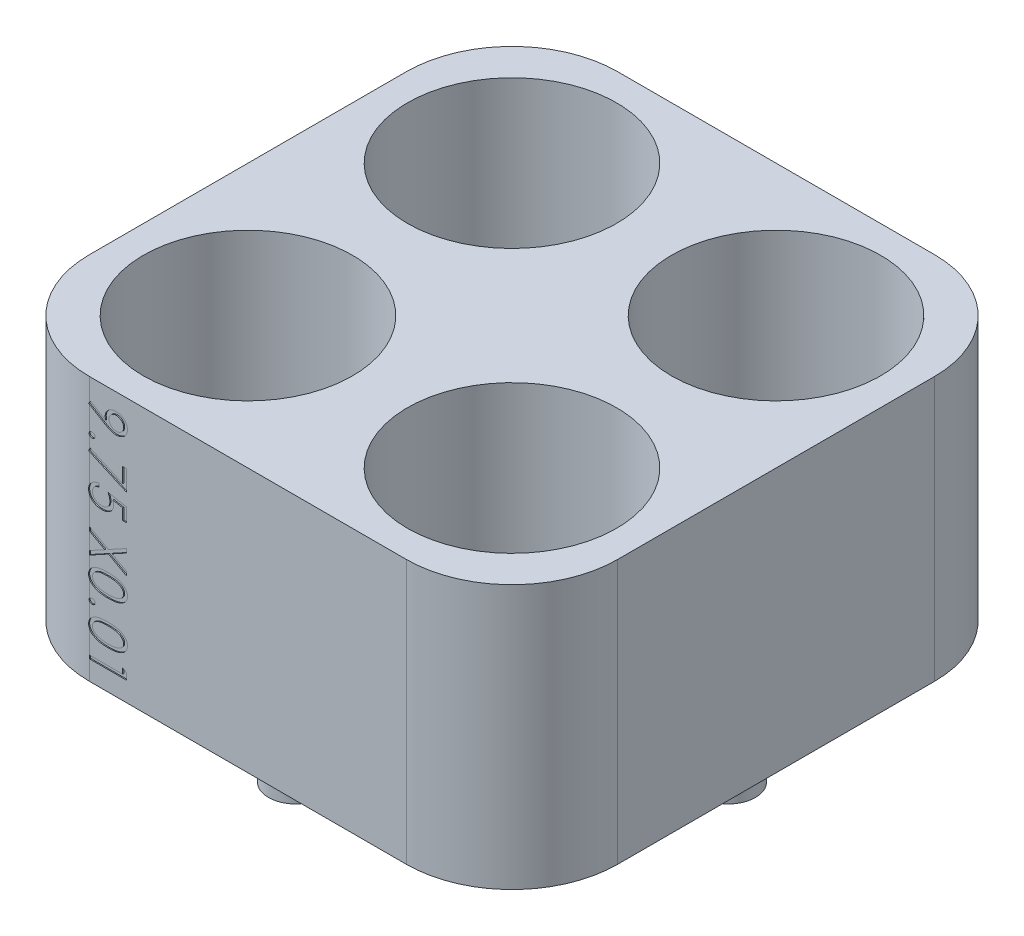
SolidWorks part; units mm, degrees
ref_plane "Alzado" through (0, 0, 0) normal (0, 0, 1) x (1, 0, 0)
ref_plane "Planta" through (0, 0, 0) normal (0, 1, 0) x (1, 0, 0)
ref_plane "Vista lateral" through (0, 0, 0) normal (1, 0, 0) x (0, 0, -1)
sketch "Croquis1" plane through (0, 0, 0) normal (0, 1, 0) x (1, 0, 0)
  line L1 (-25, 25) -> (25, 25)
  line L2 (-25, 25) -> (-25, -25)
  line L3 (-25, -25) -> (25, -25)
  line L4 (25, 25) -> (25, -25)
  line L5 (-25, 25) -> (25, -25) construction
  line L6 (-25, -25) -> (25, 25) construction
  point P0 (0, 0)
  dimension "D1" = 50
  dimension "D2" = 50
extrude "Saliente-Extruir1" add sketch "Croquis1" along normal blind 25
sketch "Croquis2" plane through (0, 25, 0) normal (0, 1, 0) x (1, 0, 0)
  line L1 (-25, 25) -> (-25, -25) construction
  line L2 (25, 25) -> (-25, 25) construction
  circle A0 centre (-12.5, 12.5) radius 9.9
  dimension "D1" = 19.8
  dimension "D2" = 12.5
  dimension "D3" = 12.5
extrude "Cortar-Extruir1" cut sketch "Croquis2" against normal blind 34
pattern_linear "MatrizL1" count 2 spacing 25 along (1, 0, 0) count 2 spacing 25 along (0, 0, 1) of "Cortar-Extruir1"
sketch "Croquis3" plane through (0, 0, 0) normal (0, -1, 0) x (1, 0, 0)
  line L0 (0, 7.2028) -> (0, 11.424) construction
  line L1 (-2.55, 0) -> (-5.3602, 0) construction
  circle A0 centre (0, 0) radius 2.55
  circle A1 centre (20.5, 0) radius 2.55
  circle A2 centre (-20.5, 0) radius 2.55
  circle A3 centre (0, 20.5) radius 2.55
  circle A4 centre (0, -20.5) radius 2.55
  dimension "D1" = 5.1
  dimension "D2" = 5.1
  dimension "D5" = 5.1
  dimension "D3" = 20.5
  dimension "D4" = 20.5
extrude "Saliente-Extruir2" add sketch "Croquis3" along normal blind 3
fillet "Redondeo3" radius 10 4 edges at (-25, 12.5, -25) (25, 12.5, -25) (25, 12.5, 25) (-25, 12.5, 25)
sketch "Croquis6" plane through (25, 0, 0) normal (1, 0, 0) x (0, 0, -1)
  line L5 (-15, 25) -> (15, 25) construction
  line L6 (-1.0144, 25) -> (5.0005, 25)
  line L7 (-1.0144, 25) -> (-1.0144, 23.8299)
  line L8 (-1.0144, 23.8299) -> (5.0005, 23.8299)
  line L9 (5.0005, 25) -> (5.0005, 23.8299)
sketch "Croquis7" plane through (0, 0, -25) normal (0, 0, -1) x (-1, 0, 0)
  line L0 (7.8632, 14.1683) -> (8.4844, 13.6947)
  line L1 (8.4844, 13.6947) -> (9.1494, 13.7051)
  line L2 (10.3053, 7.9462) -> (10.3053, 7.1749)
  line L3 (10.3053, 7.1749) -> (10.031, 7.1749)
  line L4 (10.031, 7.1749) -> (9.7567, 7.1749)
  line L5 (9.7567, 7.1749) -> (9.7567, 7.9064)
  line L6 (8.8152, 8.9851) -> (8.2479, 8.958)
  line L7 (8.2479, 8.958) -> (8.2217, 8.0664)
  line L8 (8.2217, 8.0664) -> (8.1956, 7.1749)
  line L9 (8.1956, 7.1749) -> (7.9246, 7.1749)
  line L10 (7.9246, 7.1749) -> (7.6536, 7.1749)
  line L11 (7.6536, 7.1749) -> (7.6536, 8.2734)
  line L12 (7.6536, 8.2734) -> (7.6536, 9.372)
  line L13 (7.6536, 9.372) -> (7.3564, 9.6424)
  line L14 (-2.7058, 14.0872) -> (-2.3467, 13.6793)
  line L15 (-2.3467, 13.6793) -> (-1.6645, 14.3361)
  line L16 (-1.6495, 11.3447) -> (-2.312, 11.9941)
  line L17 (-2.312, 11.9941) -> (-2.981, 11.3447)
  line L18 (-9.4499, 8.7294) -> (-8.8056, 8.7294)
  line L19 (-8.8056, 8.7294) -> (-8.8056, 8.455)
  line L20 (-8.8056, 8.455) -> (-8.8056, 8.1807)
  line L21 (-8.8056, 8.1807) -> (-9.4064, 8.1807)
  line L22 (-9.2629, 7.7692) -> (-8.577, 7.7692)
  line L23 (-8.577, 7.7692) -> (-8.577, 8.3636)
  line L24 (-8.577, 8.3636) -> (-8.577, 8.958)
  line L25 (-8.577, 8.958) -> (-9.2857, 8.9847)
  line L26 (-9.2857, 8.9847) -> (-9.9944, 9.0114)
  line L27 (-9.9944, 9.0114) -> (-9.9944, 9.2818)
  line L28 (-9.9944, 9.2818) -> (-9.9944, 9.5523)
  line L29 (-9.9944, 9.5523) -> (-9.304, 9.5523)
  line L30 (-5.4224, 9.2818) -> (-5.4224, 9.0114)
  line L31 (-5.4224, 9.0114) -> (-6.131, 8.9847)
  line L32 (-6.131, 8.9847) -> (-6.8397, 8.958)
  line L33 (-6.8397, 8.958) -> (-6.8659, 8.0664)
  line L34 (-6.8659, 8.0664) -> (-6.892, 7.1749)
  line L35 (-6.892, 7.1749) -> (-7.163, 7.1749)
  line L36 (-7.163, 7.1749) -> (-7.434, 7.1749)
  line L37 (-7.434, 7.1749) -> (-7.434, 8.1741)
  line L38 (-6.1873, 9.5523) -> (-5.4224, 9.5523)
  line L39 (-5.4224, 9.5523) -> (-5.4224, 9.2818)
  line L40 (-2.9535, 9.278) -> (-2.9535, 9.0037)
  line L41 (-2.9535, 9.0037) -> (-3.621, 9.0037)
  line L42 (-4.508, 7.9796) -> (-4.508, 7.1749)
  line L43 (-4.508, 7.1749) -> (-4.7906, 7.1749)
  line L44 (-4.7906, 7.1749) -> (-5.0732, 7.1749)
  line L45 (-5.0732, 7.1749) -> (-5.0421, 8.1431)
  line L46 (-3.7256, 9.5523) -> (-2.9535, 9.5523)
  line L47 (-2.9535, 9.5523) -> (-2.9535, 9.278)
  line L48 (-1.1662, 7.9978) -> (-1.8562, 7.9978)
  line L49 (-1.8562, 7.9978) -> (-1.8562, 8.2722)
  line L50 (-1.8562, 8.2722) -> (-1.8562, 8.5465)
  line L51 (-1.8562, 8.5465) -> (-1.2098, 8.5465)
  line L52 (-1.3075, 8.958) -> (-1.9934, 8.958)
  line L53 (-1.9934, 8.958) -> (-1.9934, 8.3636)
  line L54 (-1.9934, 8.3636) -> (-1.9934, 7.7692)
  line L55 (-1.9934, 7.7692) -> (-1.3761, 7.7422)
  line L56 (-1.3761, 7.7422) -> (-0.7589, 7.7152)
  line L57 (-0.7589, 7.7152) -> (-0.7589, 7.4353)
  line L58 (-0.7589, 7.4353) -> (-0.7589, 7.1555)
  line L59 (-0.7589, 7.1555) -> (-1.4994, 7.1891)
  line L60 (2.4415, 9.2818) -> (2.4415, 9.0114)
  line L61 (2.4415, 9.0114) -> (1.7328, 8.9847)
  line L62 (1.7328, 8.9847) -> (1.0242, 8.958)
  line L63 (1.0242, 8.958) -> (0.998, 8.0664)
  line L64 (0.998, 8.0664) -> (0.9718, 7.1749)
  line L65 (0.9718, 7.1749) -> (0.7008, 7.1749)
  line L66 (0.7008, 7.1749) -> (0.4298, 7.1749)
  line L67 (0.4298, 7.1749) -> (0.4298, 8.1741)
  line L68 (1.6766, 9.5523) -> (2.4415, 9.5523)
  line L69 (2.4415, 9.5523) -> (2.4415, 9.2818)
  line L70 (3.6718, 8.7294) -> (4.3617, 8.7294)
  line L71 (4.3617, 8.7294) -> (4.3617, 8.455)
  line L72 (4.3617, 8.455) -> (4.3617, 8.1807)
  line L73 (4.3617, 8.1807) -> (3.7153, 8.1807)
  line L74 (3.7641, 9.0037) -> (3.0816, 9.0037)
  line L75 (3.0816, 9.0037) -> (3.0816, 9.278)
  line L76 (3.0816, 9.278) -> (3.0816, 9.5523)
  line L77 (3.0816, 9.5523) -> (3.863, 9.5523)
  line L78 (7.1049, 8.3636) -> (7.1049, 7.1749)
  line L79 (7.1049, 7.1749) -> (6.8306, 7.1749)
  line L80 (6.8306, 7.1749) -> (6.5563, 7.1749)
  line L81 (6.5563, 7.1749) -> (6.5563, 8.3636)
  line L82 (6.5563, 8.3636) -> (6.5563, 9.5523)
  line L83 (6.5563, 9.5523) -> (6.8306, 9.5523)
  line L84 (6.8306, 9.5523) -> (7.1049, 9.5523)
  line L85 (7.1049, 9.5523) -> (7.1049, 8.3636)
  line L86 (0.8827, 14.6336) -> (0.7629, 14.6662)
  line L87 (-13.4691, 8.7327) -> (-13.4691, 7.7235)
  line L88 (-13.4691, 7.7235) -> (-12.4632, 7.7235)
  line L89 (-12.4632, 7.7235) -> (-11.4574, 7.7235)
  line L90 (-11.4574, 7.7235) -> (-11.4574, 7.9795)
  line L91 (-12.4358, 8.455) -> (-13.1948, 8.455)
  line L92 (-13.1948, 8.455) -> (-13.1948, 8.719)
  line L93 (-12.5776, 9.7156) -> (-13.4691, 9.7418)
  line L94 (-13.4691, 9.7418) -> (-13.4691, 8.7327)
  arc A0 (7.8207, 15.7172) -> (7.8364, 15.7705) centre (7.7385, 15.7705) ccw
  arc A1 (7.7403, 15.5996) -> (7.8207, 15.7172) centre (5.4553, 17.249) ccw
  arc A2 (7.6344, 15.4624) -> (7.7403, 15.5996) centre (5.511, 17.2088) ccw
  arc A3 (7.509, 15.3169) -> (7.6344, 15.4624) centre (4.4381, 18.0912) ccw
  arc A4 (7.509, 15.3169) -> (7.3859, 15.1667) centre (9.0083, 13.9623) ccw
  arc A5 (7.3859, 15.1667) -> (7.2866, 15.015) centre (8.617, 14.2528) ccw
  arc A6 (7.2866, 15.015) -> (7.2205, 14.8813) centre (8.3511, 14.4051) ccw
  arc A7 (7.2205, 14.8813) -> (7.2118, 14.7982) centre (7.3529, 14.8255) ccw
  arc A8 (7.2118, 14.7982) -> (7.2549, 14.7131) centre (7.3828, 14.8313) ccw
  arc A9 (7.2549, 14.7131) -> (7.4157, 14.5487) centre (10.2671, 17.4976) ccw
  arc A10 (7.4157, 14.5487) -> (7.6231, 14.3611) centre (10.3207, 17.5531) ccw
  arc A11 (7.6231, 14.3611) -> (7.8632, 14.1683) centre (11.5806, 19.0439) ccw
  arc A12 (9.1494, 13.7051) -> (9.6224, 13.7371) centre (9.0782, 18.267) ccw
  arc A13 (9.6224, 13.7371) -> (9.942, 13.8238) centre (9.4861, 14.8713) ccw
  arc A14 (9.942, 13.8238) -> (10.2456, 14.0053) centre (9.39, 15.0921) ccw
  arc A15 (10.2456, 14.0053) -> (10.6786, 14.3706) centre (5.0774, 20.5705) ccw
  arc A16 (10.6786, 14.3706) -> (10.8157, 14.5072) centre (9.344, 15.8478) ccw
  arc A17 (10.8157, 14.5072) -> (10.9316, 14.6498) centre (9.6175, 15.5987) ccw
  arc A18 (10.9316, 14.6498) -> (11.0142, 14.7795) centre (9.864, 15.4207) ccw
  arc A19 (11.0142, 14.7795) -> (11.0368, 14.8667) centre (10.8577, 14.8667) ccw
  arc A20 (11.0368, 14.8667) -> (11.0138, 14.9543) centre (10.8588, 14.8667) ccw
  arc A21 (11.0138, 14.9543) -> (10.9294, 15.0856) centre (9.8293, 14.2855) ccw
  arc A22 (10.9294, 15.0856) -> (10.8111, 15.2305) centre (9.5779, 14.1027) ccw
  arc A23 (10.8111, 15.2305) -> (10.6711, 15.3696) centre (9.282, 13.8321) ccw
  arc A24 (10.531, 15.5023) -> (10.6711, 15.3696) centre (13.4494, 18.4448) ccw
  arc A25 (10.4128, 15.6274) -> (10.531, 15.5023) centre (12.3843, 17.371) ccw
  arc A26 (10.3221, 15.7353) -> (10.4128, 15.6274) centre (12.5085, 17.4808) ccw
  arc A27 (10.3053, 15.7832) -> (10.3221, 15.7353) centre (10.3821, 15.7832) ccw
  arc A28 (10.3608, 15.8219) -> (10.3053, 15.7832) centre (10.3466, 15.7832) ccw
  arc A29 (10.5656, 15.7289) -> (10.3608, 15.8219) centre (9.8279, 14.3762) ccw
  arc A30 (10.8002, 15.5792) -> (10.5656, 15.7289) centre (9.599, 13.9564) ccw
  arc A31 (10.9826, 15.4138) -> (10.8002, 15.5792) centre (10.0591, 14.578) ccw
  arc A32 (10.9826, 15.4138) -> (11.0637, 15.3403) centre (11.3967, 15.7885) ccw
  arc A33 (11.0637, 15.3403) -> (11.1631, 15.2781) centre (11.5017, 15.9299) ccw
  arc A34 (11.1631, 15.2781) -> (11.265, 15.2354) centre (11.4705, 15.8698) ccw
  arc A35 (11.265, 15.2354) -> (11.3528, 15.2216) centre (11.3528, 15.5063) ccw
  arc A36 (11.5105, 15.1947) -> (11.3528, 15.2216) centre (11.3528, 14.7446) ccw
  arc A37 (11.6455, 15.1174) -> (11.5105, 15.1947) centre (11.3692, 14.7916) ccw
  arc A38 (11.7362, 15.0028) -> (11.6455, 15.1174) centre (11.405, 14.8338) ccw
  arc A39 (11.7684, 14.8692) -> (11.7362, 15.0028) centre (11.4744, 14.8692) ccw
  arc A40 (11.7684, 14.8692) -> (11.79, 14.7971) centre (11.8993, 14.8692) ccw
  arc A41 (11.79, 14.7971) -> (11.8825, 14.6685) centre (13.4278, 15.8772) ccw
  arc A42 (11.8825, 14.6685) -> (12.0082, 14.5215) centre (13.633, 16.0377) ccw
  arc A43 (12.0082, 14.5215) -> (12.157, 14.3724) centre (14.2933, 16.654) ccw
  arc A44 (12.438, 14.0823) -> (12.157, 14.3724) centre (9.3325, 11.356) ccw
  arc A45 (12.4278, 13.9645) -> (12.438, 14.0823) centre (12.3765, 14.0283) ccw
  arc A46 (12.2881, 13.9582) -> (12.4278, 13.9645) centre (12.3537, 14.0566) ccw
  arc A47 (11.9498, 14.2059) -> (12.2881, 13.9582) centre (14.8744, 17.8451) ccw
  arc A48 (11.9498, 14.2059) -> (11.8015, 14.3147) centre (10.6506, 12.5892) ccw
  arc A49 (11.8015, 14.3147) -> (11.6481, 14.4066) centre (10.7739, 12.7741) ccw
  arc A50 (11.6481, 14.4066) -> (11.5101, 14.4719) centre (10.9149, 13.0372) ccw
  arc A51 (11.5101, 14.4719) -> (11.4191, 14.4901) centre (11.4191, 14.2524) ccw
  arc A52 (11.4191, 14.4901) -> (11.2737, 14.4365) centre (11.4191, 14.2662) ccw
  arc A53 (11.2737, 14.4365) -> (11.0199, 14.2002) centre (13.8839, 11.378) ccw
  arc A54 (11.0199, 14.2002) -> (10.703, 13.8512) centre (15.1341, 10.1459) ccw
  arc A55 (10.703, 13.8512) -> (10.3171, 13.3718) centre (23.3414, 3.2831) ccw
  arc A56 (10.3171, 13.3718) -> (10.2657, 13.2677) centre (10.5478, 13.1931) ccw
  arc A57 (10.2657, 13.2677) -> (10.2276, 13.0849) centre (11.9738, 12.816) ccw
  arc A58 (10.2276, 13.0849) -> (10.2027, 12.8512) centre (12.7023, 12.7038) ccw
  arc A59 (10.2027, 12.8512) -> (10.1946, 12.5765) centre (14.86, 12.5765) ccw
  arc A60 (10.1946, 12.5765) -> (10.204, 12.2376) centre (16.3162, 12.5765) ccw
  arc A61 (10.204, 12.2376) -> (10.2357, 12.0059) centre (11.6523, 12.3179) ccw
  arc A62 (10.2357, 12.0059) -> (10.2978, 11.8205) centre (11.1359, 12.2042) ccw
  arc A63 (10.2978, 11.8205) -> (10.4015, 11.6373) centre (11.4166, 12.3327) ccw
  arc A64 (10.4015, 11.6373) -> (10.6632, 11.2924) centre (14.0932, 14.1663) ccw
  arc A65 (10.6632, 11.2924) -> (10.9626, 10.9662) centre (14.4096, 14.4314) ccw
  arc A66 (10.9626, 10.9662) -> (11.2451, 10.7049) centre (14.694, 14.7173) ccw
  arc A67 (11.2451, 10.7049) -> (11.3944, 10.6496) centre (11.3944, 10.8787) ccw
  arc A68 (11.3944, 10.6496) -> (11.4678, 10.669) centre (11.3944, 10.7979) ccw
  arc A69 (11.4678, 10.669) -> (11.591, 10.7467) centre (10.6583, 12.0903) ccw
  arc A70 (11.591, 10.7467) -> (11.7308, 10.8535) centre (10.4984, 12.3206) ccw
  arc A71 (11.7308, 10.8535) -> (11.8705, 10.98) centre (10.1105, 12.7824) ccw
  arc A72 (12.1865, 11.2633) -> (11.8705, 10.98) centre (15.333, 7.434) ccw
  arc A73 (12.3254, 11.2717) -> (12.1865, 11.2633) centre (12.2618, 11.1718) ccw
  arc A74 (12.3462, 11.1583) -> (12.3254, 11.2717) centre (12.2831, 11.2053) ccw
  arc A75 (12.0866, 10.8425) -> (12.3462, 11.1583) centre (8.8334, 13.7815) ccw
  arc A76 (12.0866, 10.8425) -> (11.9503, 10.6793) centre (14.1042, 9.0197) ccw
  arc A77 (11.9503, 10.6793) -> (11.8331, 10.5124) centre (13.7779, 9.2711) ccw
  arc A78 (11.8331, 10.5124) -> (11.7469, 10.3632) centre (13.4831, 9.4593) ccw
  arc A79 (11.7469, 10.3632) -> (11.7198, 10.2678) centre (11.9646, 10.2498) ccw
  arc A80 (11.6821, 10.1339) -> (11.7198, 10.2678) centre (11.3722, 10.2934) ccw
  arc A81 (11.5944, 10.0217) -> (11.6821, 10.1339) centre (11.3432, 10.3083) ccw
  arc A82 (11.4687, 9.9467) -> (11.5944, 10.0217) centre (11.3273, 10.3265) ccw
  arc A83 (11.3222, 9.9195) -> (11.4687, 9.9467) centre (11.3174, 10.353) ccw
  arc A84 (11.3222, 9.9195) -> (11.2525, 9.9004) centre (11.3238, 9.7769) ccw
  arc A85 (11.2525, 9.9004) -> (11.124, 9.8199) centre (12.3164, 8.0596) ccw
  arc A86 (11.124, 9.8199) -> (10.9761, 9.711) centre (12.4479, 7.8656) ccw
  arc A87 (10.9761, 9.711) -> (10.8246, 9.5823) centre (12.9922, 7.183) ccw
  arc A88 (10.5215, 9.3355) -> (10.8246, 9.5823) centre (8.2644, 12.4162) ccw
  arc A89 (10.4143, 9.3612) -> (10.5215, 9.3355) centre (10.4788, 9.3938) ccw
  arc A90 (10.43, 9.5064) -> (10.4143, 9.3612) centre (10.534, 9.4217) ccw
  arc A91 (10.7064, 9.816) -> (10.43, 9.5064) centre (14.0228, 6.5776) ccw
  arc A92 (10.7064, 9.816) -> (10.8329, 9.9529) centre (8.2825, 12.1828) ccw
  arc A93 (10.8329, 9.9529) -> (10.9398, 10.0845) centre (9.0895, 11.4772) ccw
  arc A94 (10.9398, 10.0845) -> (11.0198, 10.1981) centre (9.1777, 11.4109) ccw
  arc A95 (11.0198, 10.1981) -> (11.0368, 10.255) centre (10.9335, 10.255) ccw
  arc A96 (11.0368, 10.255) -> (10.9841, 10.3809) centre (10.86, 10.255) ccw
  arc A97 (10.9841, 10.3809) -> (10.491, 10.8589) centre (-17.2866, -18.295) ccw
  arc A98 (10.491, 10.8589) -> (9.9956, 11.3213) centre (-12.443, -13.2114) ccw
  arc A99 (9.9956, 11.3213) -> (9.8429, 11.3925) centre (9.806, 11.1141) ccw
  arc A100 (9.8429, 11.3925) -> (9.4672, 11.4208) centre (9.4061, 8.0975) ccw
  arc A101 (9.4672, 11.4208) -> (8.9452, 11.4189) centre (9.2489, -0.4536) ccw
  arc A102 (8.9452, 11.4189) -> (8.4316, 11.3984) centre (9.4014, -6.4151) ccw
  arc A103 (8.4316, 11.3984) -> (8.2536, 11.3519) centre (8.4566, 10.9386) ccw
  arc A104 (8.2536, 11.3519) -> (7.9869, 11.175) centre (8.8016, 10.2362) ccw
  arc A105 (7.9869, 11.175) -> (7.6125, 10.8268) centre (12.8611, 5.5589) ccw
  arc A106 (7.6125, 10.8268) -> (7.2577, 10.4565) centre (15.4297, 2.9809) ccw
  arc A107 (7.2577, 10.4565) -> (7.1964, 10.2985) centre (7.4305, 10.2985) ccw
  arc A108 (7.1964, 10.2985) -> (7.2145, 10.2244) centre (7.3572, 10.2985) ccw
  arc A109 (7.2145, 10.2244) -> (7.2822, 10.1089) centre (8.3772, 10.8285) ccw
  arc A110 (7.2822, 10.1089) -> (7.3767, 9.9798) centre (8.6008, 10.9755) ccw
  arc A111 (7.3767, 9.9798) -> (7.4886, 9.8538) centre (8.8808, 11.2032) ccw
  arc A112 (7.4886, 9.8538) -> (7.6904, 9.6721) centre (8.9275, 11.2485) ccw
  arc A113 (7.6904, 9.6721) -> (7.8549, 9.5907) centre (7.9674, 10.025) ccw
  arc A114 (7.8549, 9.5907) -> (8.0864, 9.5585) centre (8.1095, 10.5738) ccw
  arc A115 (8.0864, 9.5585) -> (8.6545, 9.552) centre (8.6644, 35.0044) ccw
  arc A116 (9.1215, 9.544) -> (8.6545, 9.552) centre (8.649, -4.5201) ccw
  arc A117 (9.4164, 9.5162) -> (9.1215, 9.544) centre (9.0393, 7.0978) ccw
  arc A118 (9.6332, 9.4615) -> (9.4164, 9.5162) centre (9.2303, 8.3229) ccw
  arc A119 (9.8275, 9.3691) -> (9.6332, 9.4615) centre (9.2866, 8.4818) ccw
  arc A120 (10.07, 9.1656) -> (9.8275, 9.3691) centre (9.2785, 8.4685) ccw
  arc A121 (10.2136, 8.9165) -> (10.07, 9.1656) centre (9.5244, 8.685) ccw
  arc A122 (10.2855, 8.5518) -> (10.2136, 8.9165) centre (8.8473, 8.4577) ccw
  arc A123 (10.3053, 7.9462) -> (10.2855, 8.5518) centre (1.0313, 7.9462) ccw
  arc A124 (9.7567, 7.9064) -> (9.7228, 8.5244) centre (4.1088, 7.9064) ccw
  arc A125 (9.7228, 8.5244) -> (9.5911, 8.8245) centre (9.1787, 8.4645) ccw
  arc A126 (9.5911, 8.8245) -> (9.3262, 8.9654) centre (9.2738, 8.5476) ccw
  arc A127 (9.3262, 8.9654) -> (8.8152, 8.9851) centre (8.9569, 6.0198) ccw
  arc A128 (7.3564, 9.6424) -> (7.2288, 9.746) centre (6.3626, 8.55) ccw
  arc A129 (7.2288, 9.746) -> (7.0914, 9.8341) centre (6.3868, 8.5834) ccw
  arc A130 (7.0914, 9.8341) -> (6.9639, 9.8963) centre (6.5037, 8.7908) ccw
  arc A131 (6.9639, 9.8963) -> (6.8717, 9.9154) centre (6.8682, 9.6665) ccw
  arc A132 (6.7131, 9.9457) -> (6.8717, 9.9154) centre (6.8784, 10.381) ccw
  arc A133 (6.5817, 10.028) -> (6.7131, 9.9457) centre (6.8541, 10.3171) ccw
  arc A134 (6.4953, 10.1513) -> (6.5817, 10.028) centre (6.8364, 10.2983) ccw
  arc A135 (6.4648, 10.2988) -> (6.4953, 10.1513) centre (6.8376, 10.2988) ccw
  arc A136 (6.4648, 10.2988) -> (6.4415, 10.3832) centre (6.3005, 10.2988) ccw
  arc A137 (6.4415, 10.3832) -> (6.3508, 10.5191) centre (5.0271, 9.5374) ccw
  arc A138 (6.3508, 10.5191) -> (6.2253, 10.6717) centre (4.7662, 9.3438) ccw
  arc A139 (6.2253, 10.6717) -> (6.0768, 10.8221) centre (4.3143, 8.9327) ccw
  arc A140 (5.9325, 10.9654) -> (6.0768, 10.8221) centre (8.2667, 13.1698) ccw
  arc A141 (5.8213, 11.0963) -> (5.9325, 10.9654) centre (7.1292, 12.0955) ccw
  arc A142 (5.7469, 11.2041) -> (5.8213, 11.0963) centre (6.8945, 11.9163) ccw
  arc A143 (5.7519, 11.2473) -> (5.7469, 11.2041) centre (5.7767, 11.2225) ccw
  arc A144 (5.8578, 11.2647) -> (5.7519, 11.2473) centre (5.8169, 11.1823) ccw
  arc A145 (6.131, 11.1127) -> (5.8578, 11.2647) centre (4.3782, 8.2823) ccw
  arc A146 (6.3917, 10.9301) -> (6.131, 11.1127) centre (4.6509, 8.7227) ccw
  arc A147 (6.4986, 10.7849) -> (6.3917, 10.9301) centre (6.1812, 10.6631) ccw
  arc A148 (6.4986, 10.7849) -> (6.6024, 10.6772) centre (6.6776, 10.8536) ccw
  arc A149 (6.6024, 10.6772) -> (6.7608, 10.6678) centre (6.6948, 10.8938) ccw
  arc A150 (6.7608, 10.6678) -> (6.9698, 10.7749) centre (6.5856, 11.2676) ccw
  arc A151 (6.9698, 10.7749) -> (7.2092, 10.9925) centre (5.6507, 12.4663) ccw
  arc A152 (7.2092, 10.9925) -> (7.6024, 11.44) centre (1.2864, 16.5932) ccw
  arc A153 (7.6024, 11.44) -> (7.8101, 11.7698) centre (6.3648, 12.4497) ccw
  arc A154 (7.8101, 11.7698) -> (7.9156, 12.1133) centre (6.658, 12.3118) ccw
  arc A155 (7.9156, 12.1133) -> (7.9614, 12.5915) centre (4.0276, 12.7269) ccw
  arc A156 (7.9614, 12.5915) -> (7.9658, 12.9697) centre (-0.2685, 12.8749) ccw
  arc A157 (7.9658, 12.9697) -> (7.9414, 13.1961) centre (6.7728, 12.9559) ccw
  arc A158 (7.9414, 13.1961) -> (7.8789, 13.3759) centre (7.2334, 13.0506) ccw
  arc A159 (7.8789, 13.3759) -> (7.7592, 13.5757) centre (6.4557, 12.6586) ccw
  arc A160 (7.7592, 13.5757) -> (7.479, 13.9431) centre (2.8327, 10.1098) ccw
  arc A161 (7.479, 13.9431) -> (7.2074, 14.235) centre (4.8934, 11.8099) ccw
  arc A162 (7.2074, 14.235) -> (6.9674, 14.4357) centre (5.5572, 12.5055) ccw
  arc A163 (6.9674, 14.4357) -> (6.8009, 14.4901) centre (6.8009, 14.2078) ccw
  arc A164 (6.8009, 14.4901) -> (6.7093, 14.4691) centre (6.8009, 14.2792) ccw
  arc A165 (6.7093, 14.4691) -> (6.5669, 14.3915) centre (7.4157, 13.0051) ccw
  arc A166 (6.5669, 14.3915) -> (6.4078, 14.2829) centre (7.5845, 12.7294) ccw
  arc A167 (6.4078, 14.2829) -> (6.2526, 14.1543) centre (7.8163, 12.4235) ccw
  arc A168 (5.9495, 13.9075) -> (6.2526, 14.1543) centre (3.6924, 16.9882) ccw
  arc A169 (5.8423, 13.9332) -> (5.9495, 13.9075) centre (5.9068, 13.9658) ccw
  arc A170 (5.858, 14.0784) -> (5.8423, 13.9332) centre (5.962, 13.9937) ccw
  arc A171 (6.1344, 14.388) -> (5.858, 14.0784) centre (9.4508, 11.1496) ccw
  arc A172 (6.1344, 14.388) -> (6.2609, 14.5277) centre (4.3353, 16.1447) ccw
  arc A173 (6.2609, 14.5277) -> (6.3678, 14.6675) centre (4.7953, 15.7585) ccw
  arc A174 (6.3678, 14.6675) -> (6.4454, 14.7907) centre (5.0259, 15.5984) ccw
  arc A175 (6.4454, 14.7907) -> (6.4648, 14.8643) centre (6.3162, 14.8643) ccw
  arc A176 (6.4958, 14.9979) -> (6.4648, 14.8643) centre (6.7686, 14.8643) ccw
  arc A177 (6.5836, 15.1144) -> (6.4958, 14.9979) centre (6.8417, 14.8285) ccw
  arc A178 (6.7126, 15.1939) -> (6.5836, 15.1144) centre (6.8641, 14.8037) ccw
  arc A179 (6.8607, 15.2216) -> (6.7126, 15.1939) centre (6.8607, 14.8125) ccw
  arc A180 (6.8607, 15.2216) -> (6.9513, 15.2418) centre (6.8607, 15.4347) ccw
  arc A181 (6.9513, 15.2418) -> (7.0893, 15.3156) centre (6.3077, 16.6115) ccw
  arc A182 (7.0893, 15.3156) -> (7.2427, 15.4191) centre (6.1486, 16.8752) ccw
  arc A183 (7.2427, 15.4191) -> (7.3913, 15.5416) centre (5.9615, 17.1242) ccw
  arc A184 (7.6394, 15.7605) -> (7.3913, 15.5416) centre (16.6562, 5.2864) ccw
  arc A185 (7.7547, 15.8381) -> (7.6394, 15.7605) centre (8.0247, 15.3129) ccw
  arc A186 (7.8098, 15.8308) -> (7.7547, 15.8381) centre (7.777, 15.7948) ccw
  arc A187 (7.8364, 15.7705) -> (7.8098, 15.8308) centre (7.7548, 15.7705) ccw
  arc A188 (-4.1735, 15.2369) -> (-4.6255, 15.4401) centre (-5.4338, 13.0378) ccw
  arc A189 (-3.6355, 14.8943) -> (-4.1735, 15.2369) centre (-7.5658, 9.3178) ccw
  arc A190 (-3.1136, 14.4889) -> (-3.6355, 14.8943) centre (-7.7378, 9.0737) ccw
  arc A191 (-2.7058, 14.0872) -> (-3.1136, 14.4889) centre (-5.7294, 11.4256) ccw
  arc A192 (-1.0017, 14.9126) -> (-1.6645, 14.3361) centre (4.3593, 8.0795) ccw
  arc A193 (-0.4217, 15.2765) -> (-1.0017, 14.9126) centre (1.0153, 12.3417) ccw
  arc A194 (0.1537, 15.4744) -> (-0.4217, 15.2765) centre (0.6598, 13.0678) ccw
  arc A195 (0.7956, 15.5407) -> (0.1537, 15.4744) centre (0.7915, 12.4417) ccw
  arc A196 (1.1847, 15.5292) -> (0.7956, 15.5407) centre (0.7865, 8.6665) ccw
  arc A197 (1.4476, 15.4913) -> (1.1847, 15.5292) centre (1.0942, 13.9692) ccw
  arc A198 (1.6838, 15.4122) -> (1.4476, 15.4913) centre (1.151, 14.2139) ccw
  arc A199 (1.9772, 15.2664) -> (1.6838, 15.4122) centre (0.1274, 11.9118) ccw
  arc A200 (2.3788, 14.9896) -> (1.9772, 15.2664) centre (0.7926, 13.1182) ccw
  arc A201 (2.763, 14.6116) -> (2.3788, 14.9896) centre (0.0248, 12.2123) ccw
  arc A202 (3.0797, 14.1901) -> (2.763, 14.6116) centre (0.1218, 12.2973) ccw
  arc A203 (3.2772, 13.7827) -> (3.0797, 14.1901) centre (1.4583, 13.1525) ccw
  arc A204 (3.3233, 13.6068) -> (3.2772, 13.7827) centre (2.1631, 13.3967) ccw
  arc A205 (3.3622, 13.3516) -> (3.3233, 13.6068) centre (-1.2114, 12.7856) ccw
  arc A206 (3.3893, 13.0687) -> (3.3622, 13.3516) centre (-1.7499, 12.7189) ccw
  arc A207 (3.399, 12.7984) -> (3.3893, 13.0687) centre (-0.8303, 12.7815) ccw
  arc A208 (3.3017, 12.0425) -> (3.399, 12.7984) centre (0.506, 12.7868) ccw
  arc A209 (3.0106, 11.3734) -> (3.3017, 12.0425) centre (0.9449, 12.67) ccw
  arc A210 (2.5277, 10.8085) -> (3.0106, 11.3734) centre (0.8575, 12.7249) ccw
  arc A211 (1.8674, 10.3584) -> (2.5277, 10.8085) centre (0.3078, 13.3556) ccw
  arc A212 (1.6445, 10.2614) -> (1.8674, 10.3584) centre (1.0576, 11.9146) ccw
  arc A213 (1.4171, 10.1997) -> (1.6445, 10.2614) centre (1.1262, 11.7213) ccw
  arc A214 (1.1489, 10.1657) -> (1.4171, 10.1997) centre (1.0129, 12.3142) ccw
  arc A215 (0.7956, 10.1535) -> (1.1489, 10.1657) centre (0.7595, 16.3192) ccw
  arc A216 (0.1493, 10.217) -> (0.7956, 10.1535) centre (0.7772, 13.2854) ccw
  arc A217 (-0.427, 10.4128) -> (0.1493, 10.217) centre (0.6358, 12.5941) ccw
  arc A218 (-1.0017, 10.7741) -> (-0.427, 10.4128) centre (0.9552, 13.2498) ccw
  arc A219 (-1.6495, 11.3447) -> (-1.0017, 10.7741) centre (4.0247, 17.1332) ccw
  arc A220 (-3.6326, 10.7749) -> (-2.981, 11.3447) centre (-8.7936, 17.3333) ccw
  arc A221 (-4.2072, 10.414) -> (-3.6326, 10.7749) centre (-5.6168, 13.2963) ccw
  arc A222 (-4.7806, 10.2172) -> (-4.2072, 10.414) centre (-5.2824, 12.6125) ccw
  arc A223 (-5.4224, 10.1507) -> (-4.7806, 10.2172) centre (-5.4216, 13.2772) ccw
  arc A224 (-5.9428, 10.1875) -> (-5.4224, 10.1507) centre (-5.4215, 13.8704) ccw
  arc A225 (-6.3703, 10.299) -> (-5.9428, 10.1875) centre (-5.6718, 12.1016) ccw
  arc A226 (-6.7684, 10.507) -> (-6.3703, 10.299) centre (-5.6435, 12.1747) ccw
  arc A227 (-7.1992, 10.8393) -> (-6.7684, 10.507) centre (-4.3734, 14.0577) ccw
  arc A228 (-7.628, 11.3675) -> (-7.1992, 10.8393) centre (-5.8601, 12.3645) ccw
  arc A229 (-7.93, 12.0833) -> (-7.628, 11.3675) centre (-4.6606, 13.0409) ccw
  arc A230 (-8.0632, 12.8536) -> (-7.93, 12.0833) centre (-4.6226, 13.052) ccw
  arc A231 (-7.9916, 13.5443) -> (-8.0632, 12.8536) centre (-5.8998, 12.9784) ccw
  arc A232 (-7.7267, 14.1527) -> (-7.9916, 13.5443) centre (-5.7966, 12.9505) ccw
  arc A233 (-7.2696, 14.7396) -> (-7.7267, 14.1527) centre (-4.7051, 12.2706) ccw
  arc A234 (-6.7051, 15.2141) -> (-7.2696, 14.7396) centre (-4.7436, 12.3076) ccw
  arc A235 (-6.1205, 15.4878) -> (-6.7051, 15.2141) centre (-5.5415, 13.4899) ccw
  arc A236 (-5.767, 15.558) -> (-6.1205, 15.4878) centre (-5.537, 13.4743) ccw
  arc A237 (-5.3825, 15.573) -> (-5.767, 15.558) centre (-5.469, 12.8582) ccw
  arc A238 (-4.9932, 15.5333) -> (-5.3825, 15.573) centre (-5.4718, 12.7708) ccw
  arc A239 (-4.6255, 15.4401) -> (-4.9932, 15.5333) centre (-5.4167, 13.0887) ccw
  arc A240 (-11.1477, 9.8357) -> (-11.2454, 9.9892) centre (-12.2316, 9.2535) ccw
  arc A241 (-11.1073, 9.7094) -> (-11.1477, 9.8357) centre (-11.4682, 9.6636) ccw
  arc A242 (-11.1098, 9.5586) -> (-11.1073, 9.7094) centre (-11.6324, 9.6428) ccw
  arc A243 (-11.1588, 9.3072) -> (-11.1098, 9.5586) centre (-14.9842, 10.1826) ccw
  arc A244 (-11.1588, 9.3072) -> (-11.2075, 9.0588) centre (-7.2141, 8.4045) ccw
  arc A245 (-11.2075, 9.0588) -> (-11.211, 8.9103) centre (-10.6769, 8.9718) ccw
  arc A246 (-11.211, 8.9103) -> (-11.1734, 8.79) centre (-10.877, 8.9488) ccw
  arc A247 (-11.1734, 8.79) -> (-11.0833, 8.6523) centre (-10.3418, 9.2356) ccw
  arc A248 (-10.9464, 8.3681) -> (-11.0833, 8.6523) centre (-11.6578, 8.2004) ccw
  arc A249 (-10.9027, 7.9815) -> (-10.9464, 8.3681) centre (-12.542, 7.992) ccw
  arc A250 (-10.9507, 7.6059) -> (-10.9027, 7.9815) centre (-12.4755, 7.9916) ccw
  arc A251 (-11.0916, 7.3578) -> (-10.9507, 7.6059) centre (-11.4715, 7.7376) ccw
  arc A252 (-11.2431, 7.2577) -> (-11.0916, 7.3578) centre (-11.4122, 7.6783) ccw
  arc A253 (-11.4485, 7.2044) -> (-11.2431, 7.2577) centre (-11.5527, 8.028) ccw
  arc A254 (-11.7931, 7.1802) -> (-11.4485, 7.2044) centre (-11.8372, 10.2753) ccw
  arc A255 (-12.5364, 7.1749) -> (-11.7931, 7.1802) centre (-12.5364, 59.3435) ccw
  arc A256 (-13.1097, 7.1811) -> (-12.5364, 7.1749) centre (-12.5364, 33.73) ccw
  arc A257 (-13.5165, 7.2017) -> (-13.1097, 7.1811) centre (-12.9587, 14.1743) ccw
  arc A258 (-13.8053, 7.2334) -> (-13.5165, 7.2017) centre (-13.1246, 12.1001) ccw
  arc A259 (-13.908, 7.2846) -> (-13.8053, 7.2334) centre (-13.7802, 7.4124) ccw
  arc A260 (-13.9922, 7.4804) -> (-13.908, 7.2846) centre (-13.7044, 7.4882) ccw
  arc A261 (-14.0195, 8.7564) -> (-13.9922, 7.4804) centre (98.3572, 10.5257) ccw
  arc A262 (-14.0326, 10.035) -> (-14.0195, 8.7564) centre (101.8739, 10.5812) ccw
  arc A263 (-13.9543, 10.2253) -> (-14.0326, 10.035) centre (-13.7652, 10.0362) ccw
  arc A264 (-13.8976, 10.2502) -> (-13.9543, 10.2253) centre (-13.8941, 10.1651) ccw
  arc A265 (-13.5482, 10.2627) -> (-13.8976, 10.2502) centre (-12.7256, -17.6614) ccw
  arc A266 (-13.1369, 10.2686) -> (-13.5482, 10.2627) centre (-13.1495, -3.2714) ccw
  arc A267 (-12.661, 10.2634) -> (-13.1369, 10.2686) centre (-13.1594, -13.9436) ccw
  arc A268 (-11.8561, 10.2422) -> (-12.661, 10.2634) centre (-14.0796, -58.6346) ccw
  arc A269 (-11.5649, 10.2095) -> (-11.8561, 10.2422) centre (-11.9156, 8.3994) ccw
  arc A270 (-11.3946, 10.1359) -> (-11.5649, 10.2095) centre (-11.647, 9.7854) ccw
  arc A271 (-11.2454, 9.9892) -> (-11.3946, 10.1359) centre (-11.7962, 9.5783) ccw
  arc A272 (-8.1526, 9.2758) -> (-8.355, 9.4185) centre (-8.7713, 8.6134) ccw
  arc A273 (-8.0438, 9.1066) -> (-8.1526, 9.2758) centre (-8.4321, 8.9766) ccw
  arc A274 (-7.9944, 8.8403) -> (-8.0438, 9.1066) centre (-8.9671, 8.7975) ccw
  arc A275 (-7.9827, 8.3062) -> (-7.9944, 8.8403) centre (-20.1308, 8.3062) ccw
  arc A276 (-7.9903, 7.9145) -> (-7.9827, 8.3062) centre (-18.0236, 8.3062) ccw
  arc A277 (-8.0206, 7.7011) -> (-7.9903, 7.9145) centre (-9.0501, 7.9559) ccw
  arc A278 (-8.0862, 7.5491) -> (-8.0206, 7.7011) centre (-8.5095, 7.8221) ccw
  arc A279 (-8.2071, 7.3993) -> (-8.0862, 7.5491) centre (-8.8486, 8.0408) ccw
  arc A280 (-8.3641, 7.2752) -> (-8.2071, 7.3993) centre (-8.816, 8.0082) ccw
  arc A281 (-8.5268, 7.2101) -> (-8.3641, 7.2752) centre (-8.6335, 7.7122) ccw
  arc A282 (-8.7681, 7.1815) -> (-8.5268, 7.2101) centre (-8.8035, 8.5118) ccw
  arc A283 (-9.2628, 7.1749) -> (-8.7681, 7.1815) centre (-9.2628, 25.7665) ccw
  arc A284 (-9.7576, 7.1815) -> (-9.2628, 7.1749) centre (-9.2629, 25.7665) ccw
  arc A285 (-9.9989, 7.2101) -> (-9.7576, 7.1815) centre (-9.7222, 8.5118) ccw
  arc A286 (-10.1616, 7.2752) -> (-9.9989, 7.2101) centre (-9.8922, 7.7122) ccw
  arc A287 (-10.3186, 7.3993) -> (-10.1616, 7.2752) centre (-9.7097, 8.0082) ccw
  arc A288 (-10.4191, 7.5198) -> (-10.3186, 7.3993) centre (-9.7001, 8.0178) ccw
  arc A289 (-10.4889, 7.6488) -> (-10.4191, 7.5198) centre (-9.8701, 7.9001) ccw
  arc A290 (-10.5294, 7.7913) -> (-10.4889, 7.6488) centre (-9.8555, 7.906) ccw
  arc A291 (-10.543, 7.9521) -> (-10.5294, 7.7913) centre (-9.5843, 7.9521) ccw
  arc A292 (-10.5294, 8.1129) -> (-10.543, 7.9521) centre (-9.5843, 7.9521) ccw
  arc A293 (-10.4889, 8.2554) -> (-10.5294, 8.1129) centre (-9.8555, 7.9983) ccw
  arc A294 (-10.4191, 8.3844) -> (-10.4889, 8.2554) centre (-9.8701, 8.0042) ccw
  arc A295 (-10.3186, 8.5049) -> (-10.4191, 8.3844) centre (-9.7001, 7.8865) ccw
  arc A296 (-10.1709, 8.6247) -> (-10.3186, 8.5049) centre (-9.6697, 7.856) ccw
  arc A297 (-10.0216, 8.6906) -> (-10.1709, 8.6247) centre (-9.8954, 8.2022) ccw
  arc A298 (-9.8155, 8.7214) -> (-10.0216, 8.6906) centre (-9.7718, 7.7239) ccw
  arc A299 (-9.4499, 8.7294) -> (-9.8155, 8.7214) centre (-9.4499, 0.3704) ccw
  arc A300 (-9.4064, 8.1807) -> (-9.7821, 8.1762) centre (-9.4064, -7.6165) ccw
  arc A301 (-9.7821, 8.1762) -> (-9.9165, 8.1511) centre (-9.772, 7.7496) ccw
  arc A302 (-9.9165, 8.1511) -> (-9.9715, 8.0907) centre (-9.887, 8.069) ccw
  arc A303 (-9.9715, 8.0907) -> (-9.9779, 7.975) centre (-9.6832, 8.0168) ccw
  arc A304 (-9.9779, 7.975) -> (-9.9343, 7.861) centre (-9.7059, 8.0136) ccw
  arc A305 (-9.9343, 7.861) -> (-9.8507, 7.7999) centre (-9.809, 7.9447) ccw
  arc A306 (-9.8507, 7.7999) -> (-9.683, 7.7742) centre (-9.6672, 8.4377) ccw
  arc A307 (-9.683, 7.7742) -> (-9.2629, 7.7692) centre (-9.2629, 25.4122) ccw
  arc A308 (-9.0001, 9.5434) -> (-9.304, 9.5523) centre (-9.304, 4.3543) ccw
  arc A309 (-8.7294, 9.5165) -> (-9.0001, 9.5434) centre (-9.1953, 6.2114) ccw
  arc A310 (-8.5062, 9.4745) -> (-8.7294, 9.5165) centre (-9.0756, 7.0605) ccw
  arc A311 (-8.355, 9.4185) -> (-8.5062, 9.4745) centre (-8.6573, 8.8339) ccw
  arc A312 (-7.4288, 8.8108) -> (-7.434, 8.1741) centre (31.0839, 8.1741) ccw
  arc A313 (-7.4013, 9.0634) -> (-7.4288, 8.8108) centre (-6.0423, 8.7879) ccw
  arc A314 (-7.3325, 9.2188) -> (-7.4013, 9.0634) centre (-7.0143, 8.9849) ccw
  arc A315 (-7.1931, 9.3628) -> (-7.3325, 9.2188) centre (-6.7334, 8.7784) ccw
  arc A316 (-7.033, 9.46) -> (-7.1931, 9.3628) centre (-6.7135, 8.753) ccw
  arc A317 (-6.8534, 9.5166) -> (-7.033, 9.46) centre (-6.7067, 8.7381) ccw
  arc A318 (-6.6025, 9.5447) -> (-6.8534, 9.5166) centre (-6.5404, 7.8552) ccw
  arc A319 (-6.1873, 9.5523) -> (-6.6025, 9.5447) centre (-6.1873, -1.7463) ccw
  arc A320 (-3.621, 9.0037) -> (-3.8986, 8.9962) centre (-3.621, 3.8359) ccw
  arc A321 (-3.8986, 8.9962) -> (-4.1341, 8.9733) centre (-3.7516, 6.2642) ccw
  arc A322 (-4.1341, 8.9733) -> (-4.3166, 8.9393) centre (-3.8396, 6.8872) ccw
  arc A323 (-4.3166, 8.9393) -> (-4.3982, 8.8939) centre (-4.2782, 8.7739) ccw
  arc A324 (-4.3982, 8.8939) -> (-4.4455, 8.8061) centre (-4.2756, 8.7714) ccw
  arc A325 (-4.4455, 8.8061) -> (-4.4789, 8.6) centre (-1.9538, 8.2969) ccw
  arc A326 (-4.4789, 8.6) -> (-4.5009, 8.3248) centre (-0.998, 8.1823) ccw
  arc A327 (-4.5009, 8.3248) -> (-4.508, 7.9796) centre (3.9834, 7.9796) ccw
  arc A328 (-5.0166, 8.751) -> (-5.0421, 8.1431) centre (26.4441, 7.129) ccw
  arc A329 (-4.9794, 9.0068) -> (-5.0166, 8.751) centre (-3.6267, 8.6794) ccw
  arc A330 (-4.903, 9.1711) -> (-4.9794, 9.0068) centre (-4.5307, 8.8982) ccw
  arc A331 (-4.7543, 9.3318) -> (-4.903, 9.1711) centre (-4.1277, 8.6028) ccw
  arc A332 (-4.5833, 9.4508) -> (-4.7543, 9.3318) centre (-4.0867, 8.555) ccw
  arc A333 (-4.4113, 9.5153) -> (-4.5833, 9.4508) centre (-4.2803, 8.9043) ccw
  arc A334 (-4.1705, 9.5449) -> (-4.4113, 9.5153) centre (-4.1251, 8.1801) ccw
  arc A335 (-3.7256, 9.5523) -> (-4.1705, 9.5449) centre (-3.7256, -3.8112) ccw
  arc A336 (-0.1513, 9.2074) -> (-0.2518, 9.3279) centre (-0.8703, 8.7094) ccw
  arc A337 (-0.0815, 9.0784) -> (-0.1513, 9.2074) centre (-0.7003, 8.8271) ccw
  arc A338 (-0.041, 8.9359) -> (-0.0815, 9.0784) centre (-0.7149, 8.8212) ccw
  arc A339 (-0.0274, 8.7751) -> (-0.041, 8.9359) centre (-0.9861, 8.7751) ccw
  arc A340 (-0.041, 8.6143) -> (-0.0274, 8.7751) centre (-0.9861, 8.7751) ccw
  arc A341 (-0.0815, 8.4718) -> (-0.041, 8.6143) centre (-0.7149, 8.7289) ccw
  arc A342 (-0.1513, 8.3428) -> (-0.0815, 8.4718) centre (-0.7003, 8.723) ccw
  arc A343 (-0.2518, 8.2223) -> (-0.1513, 8.3428) centre (-0.8703, 8.8407) ccw
  arc A344 (-0.402, 8.1012) -> (-0.2518, 8.2223) centre (-0.8918, 8.8622) ccw
  arc A345 (-0.5545, 8.0356) -> (-0.402, 8.1012) centre (-0.6746, 8.5248) ccw
  arc A346 (-0.7694, 8.0054) -> (-0.5545, 8.0356) centre (-0.8104, 9.0778) ccw
  arc A347 (-1.1662, 7.9978) -> (-0.7694, 8.0054) centre (-1.1662, 18.3918) ccw
  arc A348 (-1.2098, 8.5465) -> (-0.802, 8.5508) centre (-1.2098, 27.8029) ccw
  arc A349 (-0.802, 8.5508) -> (-0.6589, 8.5756) centre (-0.8123, 9.0358) ccw
  arc A350 (-0.6589, 8.5756) -> (-0.6006, 8.6364) centre (-0.6875, 8.6614) ccw
  arc A351 (-0.6006, 8.6364) -> (-0.5925, 8.7522) centre (-0.8677, 8.7131) ccw
  arc A352 (-0.5925, 8.7522) -> (-0.6361, 8.8662) centre (-0.8645, 8.7136) ccw
  arc A353 (-0.6361, 8.8662) -> (-0.7197, 8.9273) centre (-0.7614, 8.7825) ccw
  arc A354 (-0.7197, 8.9273) -> (-0.8874, 8.953) centre (-0.9032, 8.2895) ccw
  arc A355 (-0.8874, 8.953) -> (-1.3075, 8.958) centre (-1.3075, -8.685) ccw
  arc A356 (-2.1182, 7.2557) -> (-1.4994, 7.1891) centre (-1.2708, 12.222) ccw
  arc A357 (-2.4111, 7.4154) -> (-2.1182, 7.2557) centre (-2.0317, 7.7628) ccw
  arc A358 (-2.5518, 7.7257) -> (-2.4111, 7.4154) centre (-2.0064, 7.786) ccw
  arc A359 (-2.5877, 8.3779) -> (-2.5518, 7.7257) centre (3.3484, 8.3779) ccw
  arc A360 (-2.5804, 8.7992) -> (-2.5877, 8.3779) centre (9.5929, 8.3779) ccw
  arc A361 (-2.5507, 9.0208) -> (-2.5804, 8.7992) centre (-1.4468, 8.76) ccw
  arc A362 (-2.4852, 9.1759) -> (-2.5507, 9.0208) centre (-2.0595, 8.9048) ccw
  arc A363 (-2.3633, 9.3279) -> (-2.4852, 9.1759) centre (-1.7309, 8.6955) ccw
  arc A364 (-2.2063, 9.4519) -> (-2.3633, 9.3279) centre (-1.7544, 8.719) ccw
  arc A365 (-2.0437, 9.5171) -> (-2.2063, 9.4519) centre (-1.9369, 9.0149) ccw
  arc A366 (-1.8023, 9.5457) -> (-2.0437, 9.5171) centre (-1.7669, 8.2154) ccw
  arc A367 (-1.3076, 9.5523) -> (-1.8023, 9.5457) centre (-1.3076, -9.0393) ccw
  arc A368 (-0.8128, 9.5457) -> (-1.3076, 9.5523) centre (-1.3075, -9.0393) ccw
  arc A369 (-0.5715, 9.5171) -> (-0.8128, 9.5457) centre (-0.8482, 8.2154) ccw
  arc A370 (-0.4088, 9.4519) -> (-0.5715, 9.5171) centre (-0.6782, 9.0149) ccw
  arc A371 (-0.2518, 9.3279) -> (-0.4088, 9.4519) centre (-0.8607, 8.719) ccw
  arc A372 (0.4351, 8.8108) -> (0.4298, 8.1741) centre (38.9478, 8.1741) ccw
  arc A373 (0.4625, 9.0634) -> (0.4351, 8.8108) centre (1.8216, 8.7879) ccw
  arc A374 (0.5314, 9.2188) -> (0.4625, 9.0634) centre (0.8495, 8.9849) ccw
  arc A375 (0.6707, 9.3628) -> (0.5314, 9.2188) centre (1.1304, 8.7784) ccw
  arc A376 (0.8308, 9.46) -> (0.6707, 9.3628) centre (1.1504, 8.753) ccw
  arc A377 (1.0104, 9.5166) -> (0.8308, 9.46) centre (1.1571, 8.7381) ccw
  arc A378 (1.2613, 9.5447) -> (1.0104, 9.5166) centre (1.3235, 7.8552) ccw
  arc A379 (1.6766, 9.5523) -> (1.2613, 9.5447) centre (1.6766, -1.7463) ccw
  arc A380 (4.9911, 9.1752) -> (4.8688, 9.3279) centre (4.2395, 8.6986) ccw
  arc A381 (5.0565, 9.0191) -> (4.9911, 9.1752) centre (4.5642, 8.9045) ccw
  arc A382 (5.0861, 8.7948) -> (5.0565, 9.0191) centre (3.9271, 8.7562) ccw
  arc A383 (5.0932, 8.3636) -> (5.0861, 8.7948) centre (-7.856, 8.3636) ccw
  arc A384 (5.0861, 7.9324) -> (5.0932, 8.3636) centre (-7.856, 8.3636) ccw
  arc A385 (5.0565, 7.7081) -> (5.0861, 7.9324) centre (3.9271, 7.971) ccw
  arc A386 (4.9911, 7.552) -> (5.0565, 7.7081) centre (4.5642, 7.8227) ccw
  arc A387 (4.8688, 7.3993) -> (4.9911, 7.552) centre (4.2395, 8.0286) ccw
  arc A388 (4.7161, 7.277) -> (4.8688, 7.3993) centre (4.2396, 8.0285) ccw
  arc A389 (4.56, 7.2116) -> (4.7161, 7.277) centre (4.4454, 7.7039) ccw
  arc A390 (4.3356, 7.1821) -> (4.56, 7.2116) centre (4.297, 8.3417) ccw
  arc A391 (3.9041, 7.1749) -> (4.3356, 7.1821) centre (3.9041, 20.1445) ccw
  arc A392 (3.3856, 7.1997) -> (3.9041, 7.1749) centre (3.9041, 12.6126) ccw
  arc A393 (2.9977, 7.2786) -> (3.3856, 7.1997) centre (3.5651, 9.0731) ccw
  arc A394 (2.7324, 7.4088) -> (2.9977, 7.2786) centre (3.2962, 8.2228) ccw
  arc A395 (2.5897, 7.5905) -> (2.7324, 7.4088) centre (2.9554, 7.7308) ccw
  arc A396 (2.5334, 7.8332) -> (2.5897, 7.5905) centre (3.4325, 7.9139) ccw
  arc A397 (2.5449, 8.0841) -> (2.5334, 7.8332) centre (3.4602, 7.9163) ccw
  arc A398 (2.6221, 8.3164) -> (2.5449, 8.0841) centre (3.4122, 7.9252) ccw
  arc A399 (2.7574, 8.5049) -> (2.6221, 8.3164) centre (3.2635, 7.9988) ccw
  arc A400 (2.9075, 8.626) -> (2.7574, 8.5049) centre (3.3973, 7.865) ccw
  arc A401 (3.0601, 8.6916) -> (2.9075, 8.626) centre (3.1802, 8.2024) ccw
  arc A402 (3.2749, 8.7218) -> (3.0601, 8.6916) centre (3.3159, 7.6494) ccw
  arc A403 (3.6718, 8.7294) -> (3.2749, 8.7218) centre (3.6718, -1.6646) ccw
  arc A404 (3.7153, 8.1807) -> (3.3075, 8.1764) centre (3.7153, -11.0757) ccw
  arc A405 (3.3075, 8.1764) -> (3.1644, 8.1516) centre (3.3178, 7.6914) ccw
  arc A406 (3.1644, 8.1516) -> (3.1061, 8.0908) centre (3.193, 8.0658) ccw
  arc A407 (3.1061, 8.0908) -> (3.0981, 7.975) centre (3.3733, 8.0141) ccw
  arc A408 (3.0981, 7.975) -> (3.1408, 7.8619) centre (3.3725, 8.0139) ccw
  arc A409 (3.1408, 7.8619) -> (3.2233, 7.7974) centre (3.2772, 7.9514) ccw
  arc A410 (3.2233, 7.7974) -> (3.3859, 7.7637) centre (3.4315, 8.3929) ccw
  arc A411 (3.3859, 7.7637) -> (3.7652, 7.7417) centre (4.3231, 20.678) ccw
  arc A412 (3.7652, 7.7417) -> (4.2309, 7.7464) centre (3.9539, 12.1179) ccw
  arc A413 (4.2309, 7.7464) -> (4.4733, 7.8303) centre (4.2005, 8.2265) ccw
  arc A414 (4.4733, 7.8303) -> (4.5971, 8.0109) centre (4.3, 8.0819) ccw
  arc A415 (4.5971, 8.0109) -> (4.636, 8.3414) centre (3.2134, 8.3414) ccw
  arc A416 (4.636, 8.3414) -> (4.6021, 8.7036) centre (2.6854, 8.3414) ccw
  arc A417 (4.6021, 8.7036) -> (4.4867, 8.8902) centre (4.3018, 8.6469) ccw
  arc A418 (4.4867, 8.8902) -> (4.253, 8.9811) centre (4.211, 8.5273) ccw
  arc A419 (4.253, 8.9811) -> (3.7641, 9.0037) centre (3.7641, 3.698) ccw
  arc A420 (4.323, 9.5454) -> (3.863, 9.5523) centre (3.863, -5.803) ccw
  arc A421 (4.555, 9.5163) -> (4.323, 9.5454) centre (4.286, 8.3105) ccw
  arc A422 (4.7141, 9.451) -> (4.555, 9.5163) centre (4.4443, 9.0202) ccw
  arc A423 (4.8688, 9.3279) -> (4.7141, 9.451) centre (4.2487, 8.7078) ccw
  arc A424 (13.2948, 9.1141) -> (13.147, 9.285) centre (12.0427, 8.1807) ccw
  arc A425 (13.371, 8.9643) -> (13.2948, 9.1141) centre (12.8974, 8.8179) ccw
  arc A426 (13.4054, 8.7701) -> (13.371, 8.9643) centre (12.612, 8.7296) ccw
  arc A427 (13.4143, 8.4207) -> (13.4054, 8.7701) centre (6.5524, 8.4207) ccw
  arc A428 (13.3581, 7.7538) -> (13.4143, 8.4207) centre (9.4297, 8.4206) ccw
  arc A429 (13.1638, 7.4005) -> (13.3581, 7.7538) centre (12.753, 7.8565) ccw
  arc A430 (12.7782, 7.2231) -> (13.1638, 7.4005) centre (12.6864, 7.9305) ccw
  arc A431 (12.0313, 7.1749) -> (12.7782, 7.2231) centre (12.0313, 12.9771) ccw
  arc A432 (11.5832, 7.1823) -> (12.0313, 7.1749) centre (12.0313, 20.7716) ccw
  arc A433 (11.3661, 7.2144) -> (11.5832, 7.1823) centre (11.615, 8.147) ccw
  arc A434 (11.2084, 7.2895) -> (11.3661, 7.2144) centre (11.4892, 7.6756) ccw
  arc A435 (11.0298, 7.4422) -> (11.2084, 7.2895) centre (12.0915, 8.5039) ccw
  arc A436 (10.8797, 7.6166) -> (11.0298, 7.4422) centre (12.1193, 8.5317) ccw
  arc A437 (10.8041, 7.7696) -> (10.8797, 7.6166) centre (11.2701, 7.9048) ccw
  arc A438 (10.7707, 7.9734) -> (10.8041, 7.7696) centre (11.6315, 8.0096) ccw
  arc A439 (10.7625, 8.3636) -> (10.7707, 7.9734) centre (20.0587, 8.3636) ccw
  arc A440 (10.7707, 8.7538) -> (10.7625, 8.3636) centre (20.0587, 8.3636) ccw
  arc A441 (10.8041, 8.9576) -> (10.7707, 8.7538) centre (11.6315, 8.7176) ccw
  arc A442 (10.8797, 9.1106) -> (10.8041, 8.9576) centre (11.2701, 8.8224) ccw
  arc A443 (11.0298, 9.285) -> (10.8797, 9.1106) centre (12.1193, 8.1955) ccw
  arc A444 (11.2111, 9.4391) -> (11.0298, 9.285) centre (12.069, 8.2459) ccw
  arc A445 (11.3722, 9.514) -> (11.2111, 9.4391) centre (11.4885, 9.0532) ccw
  arc A446 (11.5985, 9.5454) -> (11.3722, 9.514) centre (11.628, 8.5008) ccw
  arc A447 (12.0884, 9.5523) -> (11.5985, 9.5454) centre (12.0884, -7.7885) ccw
  arc A448 (12.5783, 9.5454) -> (12.0884, 9.5523) centre (12.0884, -7.7885) ccw
  arc A449 (12.8046, 9.514) -> (12.5783, 9.5454) centre (12.5488, 8.5008) ccw
  arc A450 (12.9657, 9.4391) -> (12.8046, 9.514) centre (12.6883, 9.0532) ccw
  arc A451 (13.147, 9.285) -> (12.9657, 9.4391) centre (12.1078, 8.2459) ccw
  arc A452 (6.0737, 7.457) -> (6.0665, 7.5852) centre (5.8701, 7.5098) ccw
  arc A453 (6.0079, 7.3187) -> (6.0737, 7.457) centre (5.6809, 7.5589) ccw
  arc A454 (5.894, 7.2123) -> (6.0079, 7.3187) centre (5.6685, 7.568) ccw
  arc A455 (5.765, 7.1749) -> (5.894, 7.2123) centre (5.765, 7.4159) ccw
  arc A456 (5.6636, 7.2112) -> (5.765, 7.1749) centre (5.765, 7.3346) ccw
  arc A457 (5.5887, 7.3098) -> (5.6636, 7.2112) centre (5.8331, 7.4176) ccw
  arc A458 (5.5587, 7.4465) -> (5.5887, 7.3098) centre (5.9114, 7.4521) ccw
  arc A459 (5.5835, 7.5864) -> (5.5587, 7.4465) centre (5.9324, 7.4525) ccw
  arc A460 (5.6722, 7.6839) -> (5.5835, 7.5864) centre (5.7531, 7.5213) ccw
  arc A461 (5.8249, 7.7196) -> (5.6722, 7.6839) centre (5.8241, 7.3786) ccw
  arc A462 (5.9777, 7.6832) -> (5.8249, 7.7196) centre (5.8241, 7.3775) ccw
  arc A463 (6.0665, 7.5852) -> (5.9777, 7.6832) centre (5.8955, 7.5196) ccw
  arc A464 (6.7392, 14.8558) -> (6.7461, 14.8209) centre (6.8299, 14.8558) ccw
  arc A465 (6.7461, 14.8209) -> (6.766, 14.7913) centre (6.8311, 14.8564) ccw
  arc A466 (6.766, 14.7913) -> (6.7957, 14.7714) centre (6.8311, 14.8564) ccw
  arc A467 (6.7957, 14.7714) -> (6.8306, 14.7644) centre (6.8306, 14.8551) ccw
  arc A468 (6.8306, 14.7644) -> (6.8655, 14.7714) centre (6.8306, 14.8551) ccw
  arc A469 (6.8655, 14.7714) -> (6.8952, 14.7913) centre (6.8301, 14.8564) ccw
  arc A470 (6.8952, 14.7913) -> (6.9151, 14.8209) centre (6.8301, 14.8564) ccw
  arc A471 (6.9151, 14.8209) -> (6.922, 14.8558) centre (6.8313, 14.8558) ccw
  arc A472 (6.922, 14.8558) -> (6.9151, 14.8907) centre (6.8313, 14.8558) ccw
  arc A473 (6.9151, 14.8907) -> (6.8952, 14.9204) centre (6.8301, 14.8553) ccw
  arc A474 (6.8952, 14.9204) -> (6.8655, 14.9403) centre (6.8301, 14.8553) ccw
  arc A475 (6.8655, 14.9403) -> (6.8306, 14.9473) centre (6.8306, 14.8566) ccw
  arc A476 (6.8306, 14.9473) -> (6.7957, 14.9403) centre (6.8306, 14.8566) ccw
  arc A477 (6.7957, 14.9403) -> (6.766, 14.9204) centre (6.8311, 14.8553) ccw
  arc A478 (6.766, 14.9204) -> (6.7461, 14.8907) centre (6.8311, 14.8553) ccw
  arc A479 (6.7461, 14.8907) -> (6.7392, 14.8558) centre (6.8299, 14.8558) ccw
  arc A480 (11.3112, 14.8558) -> (11.3181, 14.8209) centre (11.4019, 14.8558) ccw
  arc A481 (11.3181, 14.8209) -> (11.338, 14.7913) centre (11.4031, 14.8564) ccw
  arc A482 (11.338, 14.7913) -> (11.3677, 14.7714) centre (11.4031, 14.8564) ccw
  arc A483 (11.3677, 14.7714) -> (11.4026, 14.7644) centre (11.4026, 14.8551) ccw
  arc A484 (11.4026, 14.7644) -> (11.4375, 14.7714) centre (11.4026, 14.8551) ccw
  arc A485 (11.4375, 14.7714) -> (11.4672, 14.7913) centre (11.4021, 14.8564) ccw
  arc A486 (11.4672, 14.7913) -> (11.4871, 14.8209) centre (11.4021, 14.8564) ccw
  arc A487 (11.4871, 14.8209) -> (11.494, 14.8558) centre (11.4033, 14.8558) ccw
  arc A488 (11.494, 14.8558) -> (11.4871, 14.8907) centre (11.4033, 14.8558) ccw
  arc A489 (11.4871, 14.8907) -> (11.4672, 14.9204) centre (11.4021, 14.8553) ccw
  arc A490 (11.4672, 14.9204) -> (11.4375, 14.9403) centre (11.4021, 14.8553) ccw
  arc A491 (11.4375, 14.9403) -> (11.4026, 14.9473) centre (11.4026, 14.8566) ccw
  arc A492 (11.4026, 14.9473) -> (11.3677, 14.9403) centre (11.4026, 14.8566) ccw
  arc A493 (11.3677, 14.9403) -> (11.338, 14.9204) centre (11.4031, 14.8553) ccw
  arc A494 (11.338, 14.9204) -> (11.3181, 14.8907) centre (11.4031, 14.8553) ccw
  arc A495 (11.3181, 14.8907) -> (11.3112, 14.8558) centre (11.4019, 14.8558) ccw
  arc A496 (-5.868, 14.5324) -> (-6.2133, 14.3839) centre (-5.3803, 12.9219) ccw
  arc A497 (-6.2133, 14.3839) -> (-6.5235, 14.1604) centre (-5.3224, 12.8204) ccw
  arc A498 (-6.5235, 14.1604) -> (-6.785, 13.8716) centre (-5.274, 12.7664) ccw
  arc A499 (-6.785, 13.8716) -> (-6.9864, 13.53) centre (-5.1652, 12.6868) ccw
  arc A500 (-6.9864, 13.53) -> (-7.1323, 13.0279) centre (-5.4066, 12.7986) ccw
  arc A501 (-7.1323, 13.0279) -> (-7.113, 12.5272) centre (-5.6695, 12.8335) ccw
  arc A502 (-7.113, 12.5272) -> (-6.9245, 12.0448) centre (-5.5553, 12.8577) ccw
  arc A503 (-6.9245, 12.0448) -> (-6.5761, 11.5964) centre (-4.9633, 13.2093) ccw
  arc A504 (-6.5761, 11.5964) -> (-5.9159, 11.1545) centre (-5.1305, 13.042) ccw
  arc A505 (-5.9159, 11.1545) -> (-5.2204, 11.0742) centre (-5.4283, 12.3263) ccw
  arc A506 (-5.2204, 11.0742) -> (-4.453, 11.3803) centre (-5.5376, 12.9847) ccw
  arc A507 (-4.453, 11.3803) -> (-3.5707, 12.0954) centre (-8.1274, 16.8156) ccw
  arc A508 (-3.5707, 12.0954) -> (-3.3342, 12.3323) centre (-9.8359, 18.5852) ccw
  arc A509 (-3.3342, 12.3323) -> (-3.1348, 12.5511) centre (-7.3208, 16.1664) ccw
  arc A510 (-3.1348, 12.5511) -> (-2.9785, 12.7389) centre (-8.2357, 16.9566) ccw
  arc A511 (-2.9785, 12.7389) -> (-2.9535, 12.8101) centre (-3.0673, 12.8101) ccw
  arc A512 (-2.9535, 12.8101) -> (-3.0392, 13.0294) centre (-3.2769, 12.8101) ccw
  arc A513 (-3.0392, 13.0294) -> (-3.5452, 13.554) centre (-15.1261, 1.8788) ccw
  arc A514 (-3.5452, 13.554) -> (-4.0808, 14.0502) centre (-11.0519, 5.9862) ccw
  arc A515 (-4.0808, 14.0502) -> (-4.4788, 14.3231) centre (-5.496, 12.4132) ccw
  arc A516 (-4.4788, 14.3231) -> (-4.8789, 14.509) centre (-6.3905, 10.7336) ccw
  arc A517 (-4.8789, 14.509) -> (-5.2075, 14.5983) centre (-5.4274, 13.1391) ccw
  arc A518 (-5.2075, 14.5983) -> (-5.5205, 14.6041) centre (-5.3858, 13.4153) ccw
  arc A519 (-5.5205, 14.6041) -> (-5.868, 14.5324) centre (-5.2998, 12.6561) ccw
  arc A520 (0.4602, 14.5852) -> (0.3214, 14.5427) centre (0.724, 13.4777) ccw
  arc A521 (0.3214, 14.5427) -> (0.1392, 14.4683) centre (1.6478, 11.0335) ccw
  arc A522 (0.1392, 14.4683) -> (-0.0528, 14.378) centre (1.7906, 10.7083) ccw
  arc A523 (-0.0528, 14.378) -> (-0.2256, 14.284) centre (1.3123, 11.6605) ccw
  arc A524 (-0.2256, 14.284) -> (-0.6147, 14.0021) centre (1.0305, 12.1412) ccw
  arc A525 (-0.6147, 14.0021) -> (-1.1196, 13.5247) centre (6.2571, 6.2294) ccw
  arc A526 (-1.1196, 13.5247) -> (-1.5946, 13.0238) centre (10.6024, 1.932) ccw
  arc A527 (-1.5946, 13.0238) -> (-1.6733, 12.8202) centre (-1.3707, 12.8202) ccw
  arc A528 (-1.6733, 12.8202) -> (-1.5738, 12.5833) centre (-1.3415, 12.8202) ccw
  arc A529 (-1.5738, 12.5833) -> (-0.986, 12.0331) centre (10.5671, 24.9665) ccw
  arc A530 (-0.986, 12.0331) -> (-0.3641, 11.5167) centre (6.4865, 20.3984) ccw
  arc A531 (-0.3641, 11.5167) -> (0.0988, 11.2372) centre (1.0897, 13.4014) ccw
  arc A532 (0.0988, 11.2372) -> (0.6396, 11.0753) centre (0.95, 13.0964) ccw
  arc A533 (0.6396, 11.0753) -> (1.1446, 11.0948) centre (0.8416, 12.3906) ccw
  arc A534 (1.1446, 11.0948) -> (1.616, 11.3028) centre (0.8271, 12.4527) ccw
  arc A535 (1.616, 11.3028) -> (2.0583, 11.6953) centre (0.2688, 13.2665) ccw
  arc A536 (2.0583, 11.6953) -> (2.4526, 12.4725) centre (0.7403, 12.8525) ccw
  arc A537 (2.4526, 12.4725) -> (2.4223, 13.3407) centre (0.7601, 12.8481) ccw
  arc A538 (2.4223, 13.3407) -> (1.9737, 14.0899) centre (0.7398, 12.8421) ccw
  arc A539 (1.9737, 14.0899) -> (1.2158, 14.5383) centre (0.7002, 12.8021) ccw
  arc A540 (1.2158, 14.5383) -> (1.0415, 14.5893) centre (-4.8521, -5.8946) ccw
  arc A541 (1.0415, 14.5893) -> (0.8827, 14.6336) centre (-1.9773, 4.0972) ccw
  arc A542 (0.7629, 14.6662) -> (0.7561, 14.6636) centre (0.7613, 14.6601) ccw
  arc A543 (0.7494, 14.6588) -> (0.7561, 14.6636) centre (0.7464, 14.6701) ccw
  arc A544 (0.6666, 14.6367) -> (0.7494, 14.6588) centre (-5.6237, 38.3941) ccw
  arc A545 (0.5717, 14.6124) -> (0.6666, 14.6367) centre (-0.9639, 20.7949) ccw
  arc A546 (0.4602, 14.5852) -> (0.5717, 14.6124) centre (-2.3038, 26.1894) ccw
  arc A547 (-11.4574, 7.9795) -> (-11.5035, 8.2264) centre (-12.142, 7.9795) ccw
  arc A548 (-11.5035, 8.2264) -> (-11.6346, 8.3689) centre (-11.7502, 8.131) ccw
  arc A549 (-11.6346, 8.3689) -> (-11.8984, 8.4383) centre (-11.9421, 7.7362) ccw
  arc A550 (-11.8984, 8.4383) -> (-12.4358, 8.455) centre (-12.4358, -0.2031) ccw
  arc A551 (-13.1755, 8.8783) -> (-13.1948, 8.719) centre (-12.5265, 8.719) ccw
  arc A552 (-13.1135, 8.954) -> (-13.1755, 8.8783) centre (-13.0652, 8.8512) ccw
  arc A553 (-12.9757, 8.9906) -> (-13.1135, 8.954) centre (-12.9441, 8.5936) ccw
  arc A554 (-12.5564, 9.0191) -> (-12.9757, 8.9906) centre (-11.5208, -9.3076) ccw
  arc A555 (-12.5564, 9.0191) -> (-12.1095, 9.0579) centre (-12.9752, 16.4311) ccw
  arc A556 (-12.1095, 9.0579) -> (-11.8887, 9.1263) centre (-12.1834, 9.6873) ccw
  arc A557 (-11.8887, 9.1263) -> (-11.7709, 9.2502) centre (-12.0125, 9.3619) ccw
  arc A558 (-11.7709, 9.2502) -> (-11.7115, 9.4628) centre (-12.3975, 9.54) ccw
  arc A559 (-11.7115, 9.4628) -> (-11.7274, 9.5948) centre (-11.9987, 9.4951) ccw
  arc A560 (-11.7274, 9.5948) -> (-11.8017, 9.6642) centre (-11.8333, 9.5559) ccw
  arc A561 (-11.8017, 9.6642) -> (-11.9854, 9.6944) centre (-12.0181, 8.923) ccw
  arc A562 (-11.9854, 9.6944) -> (-12.5776, 9.7156) centre (-13.9215, -36.0662) ccw
  arc A563 (11.4209, 8.8939) -> (11.3364, 8.7212) centre (11.6303, 8.6845) ccw
  arc A564 (11.3364, 8.7212) -> (11.3364, 8.006) centre (14.2015, 8.3636) ccw
  arc A565 (11.3364, 8.006) -> (11.4209, 7.8332) centre (11.6303, 8.0427) ccw
  arc A566 (11.4209, 7.8332) -> (11.6107, 7.7454) centre (11.6355, 8.0478) ccw
  arc A567 (11.6107, 7.7454) -> (12.0884, 7.7258) centre (12.0884, 13.5726) ccw
  arc A568 (12.0884, 7.7258) -> (12.5661, 7.7454) centre (12.0884, 13.5726) ccw
  arc A569 (12.5661, 7.7454) -> (12.7559, 7.8332) centre (12.5413, 8.0478) ccw
  arc A570 (12.7559, 7.8332) -> (12.7984, 7.9024) centre (12.6327, 7.9565) ccw
  arc A571 (12.7984, 7.9024) -> (12.8334, 8.0343) centre (11.6337, 8.2825) ccw
  arc A572 (12.8334, 8.0343) -> (12.8576, 8.1945) centre (11.3723, 8.3366) ccw
  arc A573 (12.8576, 8.1945) -> (12.8656, 8.3636) centre (11.09, 8.3636) ccw
  arc A574 (12.8656, 8.3636) -> (12.8576, 8.5327) centre (11.09, 8.3636) ccw
  arc A575 (12.8576, 8.5327) -> (12.8334, 8.6929) centre (11.3723, 8.3906) ccw
  arc A576 (12.8334, 8.6929) -> (12.7984, 8.8248) centre (11.6337, 8.4447) ccw
  arc A577 (12.7984, 8.8248) -> (12.7559, 8.8939) centre (12.6327, 8.7707) ccw
  arc A578 (12.7559, 8.8939) -> (12.5661, 8.9818) centre (12.5413, 8.6794) ccw
  arc A579 (12.5661, 8.9818) -> (12.0884, 9.0014) centre (12.0884, 3.1546) ccw
  arc A580 (12.0884, 9.0014) -> (11.6107, 8.9818) centre (12.0884, 3.1546) ccw
  arc A581 (11.6107, 8.9818) -> (11.4209, 8.8939) centre (11.6355, 8.6794) ccw
extrude "Cortar-Extruir3" cut sketch "Croquis7" against normal blind 0.3
sketch "Croquis8" plane through (0, 0, 25) normal (0, 0, 1) x (1, 0, 0)
  text T0 " 9.75 X0.01" font "Century Gothic" height 3.5
extrude "Cortar-Extruir4" cut sketch "Croquis8" against normal blind 0.1
